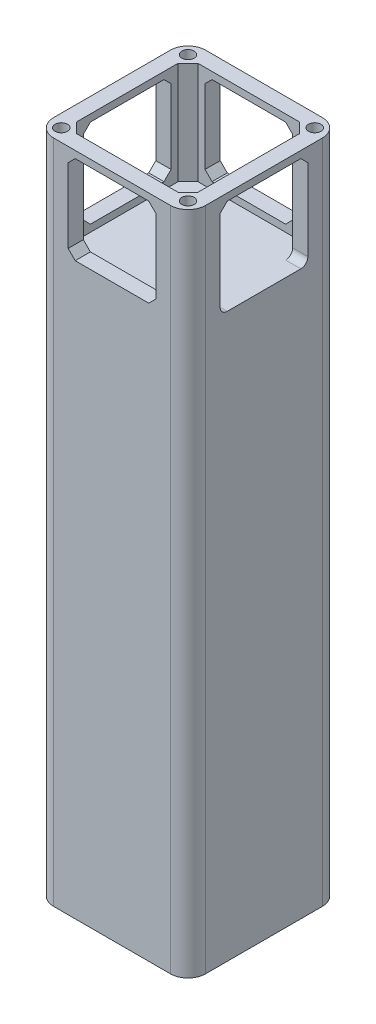
SolidWorks part; units mm, degrees
ref_plane "Front Plane" through (0, 0, 0) normal (0, 0, 1) x (1, 0, 0)
ref_plane "Top Plane" through (0, 0, 0) normal (0, 1, 0) x (1, 0, 0)
ref_plane "Right Plane" through (0, 0, 0) normal (1, 0, 0) x (0, 0, -1)
sketch "Sketch1" plane through (0, 0, 0) normal (0, 1, 0) x (1, 0, 0)
  line L1 (-20.955, -27.305) -> (20.955, -27.305)
  line L2 (-27.305, -20.955) -> (-27.305, 20.955)
  line L3 (-20.955, 27.305) -> (20.955, 27.305)
  line L4 (27.305, -20.955) -> (27.305, 20.955)
  line L5 (-27.305, -27.305) -> (27.305, 27.305) construction
  line L6 (-27.305, 27.305) -> (27.305, -27.305) construction
  arc A0 (20.955, -27.305) -> (27.305, -20.955) centre (20.955, -20.955) ccw
  arc A1 (20.955, 27.305) -> (27.305, 20.955) centre (20.955, 20.955) cw
  arc A2 (-20.955, -27.305) -> (-27.305, -20.955) centre (-20.955, -20.955) cw
  arc A3 (-27.305, 20.955) -> (-20.955, 27.305) centre (-20.955, 20.955) cw
  point P0 (0, 0)
  dimension "D3" = 6.35
  dimension "D1" = 54.61
  dimension "D2" = 54.61
extrude "Boss-Extrude1" add sketch "Sketch1" along normal blind 202.184
sketch "Sketch2" plane through (0, 0, 0) normal (0, -1, 0) x (1, 0, 0)
  line L0 (0, -27.305) -> (0, 27.305) construction
  line L1 (-20.955, 27.305) -> (20.955, 27.305) construction
  line L2 (-27.305, 0) -> (27.305, 0) construction
  line L3 (27.305, 20.955) -> (27.305, -20.955) construction
  circle A0 centre (-17.78, 17.78) radius 2.1971
  circle A1 centre (17.78, 17.78) radius 2.1971
  circle A2 centre (17.78, -17.78) radius 2.1971
  circle A3 centre (-17.78, -17.78) radius 2.1971
  point P6 (0, 0)
  point P12 (0, 0)
  dimension "D3" = 4.3942
  dimension "D1" = 17.78
  dimension "D2" = 17.78
extrude "Cut-Extrude1" cut sketch "Sketch2" against normal blind 6.7564
sketch "Sketch3" plane through (0, 202.184, 0) normal (0, 1, 0) x (1, 0, 0)
  line L0 (21.844, -18.288) -> (18.288, -21.844)
  line L1 (18.288, 21.844) -> (-18.288, 21.844)
  line L2 (21.844, 18.288) -> (21.844, -18.288)
  line L3 (18.288, -21.844) -> (-18.288, -21.844)
  line L4 (-21.844, 18.288) -> (-21.844, -18.288)
  line L5 (21.844, 21.844) -> (-21.844, -21.844) construction
  line L6 (21.844, -21.844) -> (-21.844, 21.844) construction
  line L7 (-18.288, -21.844) -> (-21.844, -18.288)
  line L8 (-18.288, 21.844) -> (-21.844, 18.288)
  line L9 (21.844, 18.288) -> (18.288, 21.844)
  line L10 (-27.305, 20.955) -> (-27.305, -20.955) construction
  line L11 (20.955, 27.305) -> (-20.955, 27.305) construction
  line L12 (27.305, -20.955) -> (27.305, 20.955) construction
  line L13 (-20.955, -27.305) -> (20.955, -27.305) construction
  line L14 (-27.305, 20.955) -> (-27.305, -20.955)
  line L15 (20.955, 27.305) -> (-20.955, 27.305)
  line L16 (27.305, -20.955) -> (27.305, 20.955)
  line L17 (-20.955, -27.305) -> (20.955, -27.305)
  arc A0 (-27.305, -20.955) -> (-20.955, -27.305) centre (-20.955, -20.955) ccw construction
  arc A1 (-20.955, 27.305) -> (-27.305, 20.955) centre (-20.955, 20.955) ccw construction
  arc A2 (27.305, 20.955) -> (20.955, 27.305) centre (20.955, 20.955) ccw construction
  arc A3 (20.955, -27.305) -> (27.305, -20.955) centre (20.955, -20.955) ccw construction
  arc A4 (-27.305, -20.955) -> (-20.955, -27.305) centre (-20.955, -20.955) ccw
  arc A5 (-20.955, 27.305) -> (-27.305, 20.955) centre (-20.955, 20.955) ccw
  arc A6 (27.305, 20.955) -> (20.955, 27.305) centre (20.955, 20.955) ccw
  arc A7 (20.955, -27.305) -> (27.305, -20.955) centre (20.955, -20.955) ccw
  point P0 (0, 0)
  dimension "D1" = 43.688
  dimension "D2" = 43.688
extrude "Boss-Extrude2" add sketch "Sketch3" along normal blind 36.83
sketch "Sketch4" plane through (21.844, 0, 0) normal (-1, 0, 0) x (0, 0, 1)
  line L0 (0, 202.184) -> (0, 239.014) construction
  line L1 (18.288, 202.184) -> (-18.288, 202.184) construction
  line L2 (18.288, 239.014) -> (-18.288, 239.014) construction
  line L3 (18.288, 239.014) -> (18.288, 202.184) construction
  line L4 (-13.208, 236.474) -> (13.208, 236.474)
  line L5 (-15.748, 233.934) -> (-15.748, 207.264)
  line L6 (-13.208, 204.724) -> (13.208, 204.724)
  line L7 (15.748, 233.934) -> (15.748, 207.264)
  line L8 (-15.748, 236.474) -> (15.748, 204.724) construction
  line L9 (-15.748, 204.724) -> (15.748, 236.474) construction
  line L10 (13.208, 236.474) -> (15.748, 233.934)
  line L11 (-15.748, 233.934) -> (-13.208, 236.474)
  line L12 (-15.748, 207.264) -> (-13.208, 204.724)
  line L13 (13.208, 204.724) -> (15.748, 207.264)
  point P6 (0, 220.599)
  dimension "D1" = 2.54
  dimension "D2" = 2.54
extrude "Cut-Extrude3" cut sketch "Sketch4" against normal up to surface (5.461 mm away) up to face at (27.305, 119.507, 0)
ref_axis "Axis1" through (0, 250.9647, 0) along (0, -1, 0)
pattern_circular "CirPattern1" count 4 over 360 about axis through (0, 250.9647, 0) along (0, -1, 0) of "Cut-Extrude3"
sketch "Sketch5" plane through (21.844, 0, 0) normal (-1, 0, 0) x (0, 0, 1)
  line L0 (15.748, 207.264) -> (15.748, 202.184)
  line L1 (15.748, 202.184) -> (-15.748, 202.184)
  line L2 (18.288, 202.184) -> (-18.288, 202.184) construction
  line L3 (-15.748, 202.184) -> (-15.748, 207.264)
  line L4 (-15.748, 207.264) -> (15.748, 207.264)
extrude "Cut-Extrude4" cut sketch "Sketch5" against normal up to surface (5.461 mm away) up to face at (27.305, 220.599, 0)
fillet "Fillet1" radius 2.54 2 edges at (24.5745, 202.184, -15.748) (24.5745, 202.184, 15.748)
sketch "Sketch6" plane through (0, 239.014, 0) normal (0, 1, 0) x (1, 0, 0)
  line L0 (20.066, -20.066) -> (25.4451, -25.4451) construction
  line L1 (18.288, -21.844) -> (21.844, -18.288) construction
  arc A0 (20.955, -27.305) -> (27.305, -20.955) centre (20.955, -20.955) ccw construction
  circle A1 centre (22.7556, -22.7556) radius 2.2225
  circle A2 centre (-22.7556, -22.7556) radius 2.2225
  circle A3 centre (-22.7556, 22.7556) radius 2.2225
  circle A4 centre (22.7556, 22.7556) radius 2.2225
  point P18 (0, 0)
  dimension "D1" = 4.445
  dimension "D2" = 4
extrude "Cut-Extrude5" cut sketch "Sketch6" against normal blind 3.81
